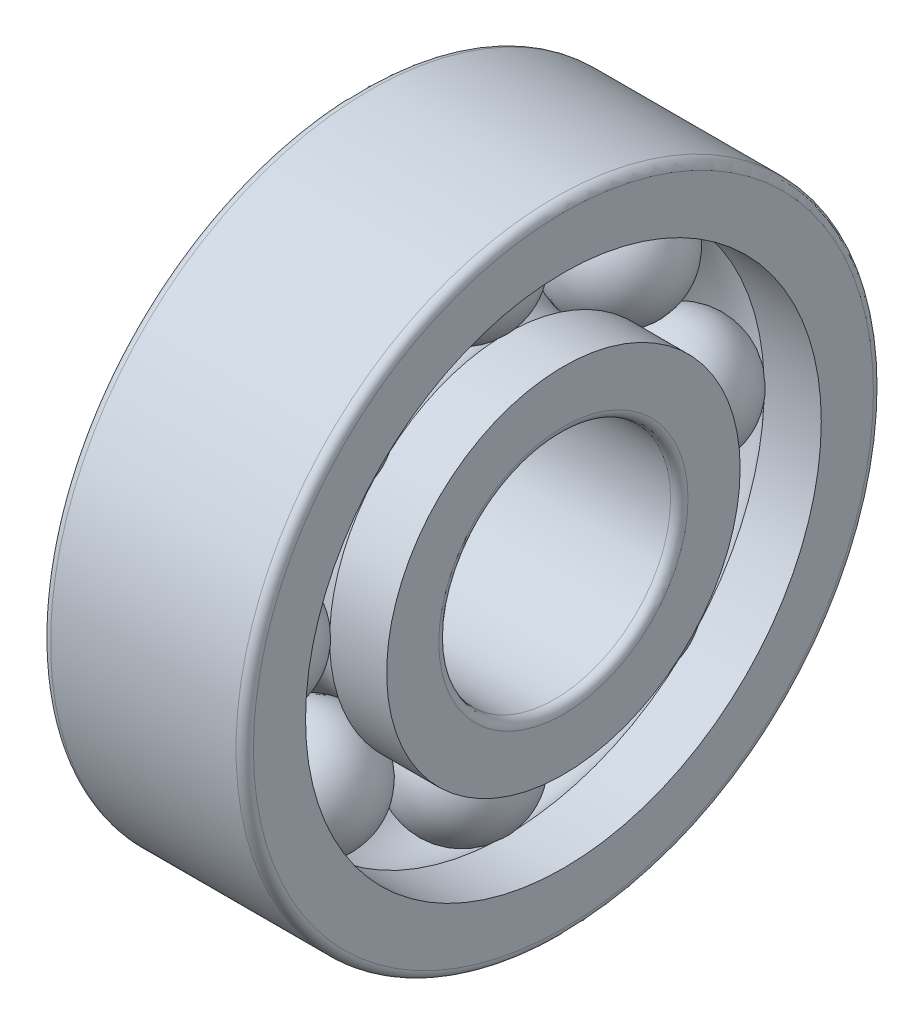
SolidWorks part; units mm, degrees
material "Alliage de zinc AC41A, brut"
ref_plane "Plane1" through (0, 0, 0) normal (0, 0, 1) x (1, 0, 0)
ref_plane "Plane2" through (0, 0, 0) normal (0, 1, 0) x (1, 0, 0)
ref_plane "Plane3" through (0, 0, 0) normal (1, 0, 0) x (0, 0, -1)
other "Configuration Table"
sketch "Clipboard" plane through (0, 0, 0) normal (0, 0, 1) x (1, 0, 0)
  line L0 (-10, 0) -> (10, 0) construction
  line L1 (0, 0) -> (22.1431, -3.112)
  line L2 (0, 0) -> (7.427, 1.0438)
  line L3 (0, 0) -> (22.1431, -3.112)
  line L4 (0, 0) -> (-22.3573, -0.3902)
  dimension "BallCLRad" = 7.5
sketch "CagSpiSke" plane through (0, 0, 0) normal (0, 0, 1) x (1, 0, 0)
  line L0 (0.21, 7.15) -> (0.21, 7.85)
  line L1 (0.21, 7.85) -> (-0.21, 7.85)
  line L2 (-0.21, 7.85) -> (-0.21, 7.15)
  line L3 (-0.21, 7.15) -> (0.21, 7.15)
  line L4 (-20.6375, 0) -> (20.6375, 0) construction
  line L5 (0, 0) -> (0, 23.7692) construction
  dimension "OD" = 15.7
  dimension "ID" = 14.3
revolve "CageSpine" add sketch "CagSpiSke" angle 0.001 about L4 reverse direction yes
ref_axis "Axis1" through (-50, 0, 0) along (1, 0, 0)
sketch "CagBalSke" plane through (0, 0, 0) normal (0, 0, 1) x (1, 0, 0)
  line L0 (-2.31, 7.5) -> (2.31, 7.5)
  line L1 (-1.905, 7.5) -> (1.905, 7.5) construction
  line L2 (-10, 0) -> (10, 0) construction
  line L3 (0, 0) -> (0, 24) construction
  arc A0 (2.31, 7.5) -> (-2.31, 7.5) centre (0, 7.5) cw
  dimension "BallCLRad" = 7.5
revolve "CageBall" [suppressed] add sketch "CagBalSke" angle 360 about L1 reverse direction yes
pattern_circular "CageBalls" [suppressed] count 8 every 45 about axis through (-50, 0, 0) along (1, 0, 0)
sketch "CagTrmODSke" plane through (0, 0, 0) normal (0, 0, 1) x (1, 0, 0)
  line L0 (2.311, 7.85) -> (2.311, 9.811)
  line L1 (2.311, 9.811) -> (-2.311, 9.811)
  line L2 (-2.311, 9.811) -> (-2.311, 7.85)
  line L3 (-2.311, 7.85) -> (2.311, 7.85)
  line L4 (-20.6375, 0) -> (20.6375, 0) construction
  line L5 (0, 0) -> (0, 25) construction
  dimension "Width" = 4.622
  dimension "ID" = 15.7
  dimension "OD" = 19.622
revolve "CageTrimOD" [suppressed] cut sketch "CagTrmODSke" angle 360 about L4 reverse direction yes
sketch "CagTrmIDSke" plane through (0, 0, 0) normal (0, 0, 1) x (1, 0, 0)
  line L0 (2.311, 5.191) -> (2.311, 7.15)
  line L1 (2.311, 7.15) -> (-2.311, 7.15)
  line L2 (-2.311, 7.15) -> (-2.311, 5.191)
  line L3 (-2.311, 5.191) -> (2.311, 5.191)
  line L4 (-20.6375, 0) -> (20.6375, 0) construction
  line L5 (0, 0) -> (0, 25) construction
  dimension "Width" = 4.622
  dimension "ID" = 10.382
  dimension "OD" = 14.3
revolve "CageTrimID" [suppressed] cut sketch "CagTrmIDSke" angle 360 about L4 reverse direction yes
sketch "BalSimSke" plane through (0, 0, 0) normal (0, 0, 1) x (1, 0, 0)
  line L0 (-10, 0) -> (10, 0) construction
  line L1 (-10, 7.5) -> (10, 7.5) construction
  line L2 (0, 0) -> (0, 23) construction
  circle A0 centre (0, 7.5) radius 2.1
  dimension "BallCLRad" = 7.5
  dimension "Ball_diameter" = 4.2
revolve "BallsSimplified" [suppressed] add sketch "BalSimSke" angle 360 about L0
sketch "BalDetSke" plane through (0, 0, 0) normal (0, 0, 1) x (1, 0, 0)
  line L0 (-2.1, 7.5) -> (2.1, 7.5)
  line L1 (-1.905, 7.5) -> (1.905, 7.5) construction
  line L2 (0, 0) -> (0, 25) construction
  arc A0 (2.1, 7.5) -> (-2.1, 7.5) centre (0, 7.5) cw
  dimension "BallCLRad" = 7.5
  dimension "Ball_diameter" = 4.2
revolve "BallDetailed" add sketch "BalDetSke" angle 360 about L1 reverse direction yes
sketch "InnRacSke" plane through (0, 0, 0) normal (0, 0, 1) x (1, 0, 0)
  line L0 (-1.5315, 6.1) -> (-3.5, 6.1)
  line L1 (-3.5, 6.1) -> (-3.5, 4.3)
  line L2 (-3.2, 4) -> (3.2, 4)
  line L3 (3.5, 4.3) -> (3.5, 6.1)
  line L4 (3.5, 6.1) -> (1.5315, 6.1)
  line L5 (-20.6375, 0) -> (20.6375, 0) construction
  line L6 (0, 0) -> (0, 30) construction
  arc A0 (-3.5, 4.3) -> (-3.2, 4) centre (-3.2, 4.3) ccw
  arc A1 (3.2, 4) -> (3.5, 4.3) centre (3.2, 4.3) ccw
  arc A2 (1.5315, 6.1) -> (-1.5315, 6.1) centre (0, 7.5) cw
  dimension "BallCLRad" = 7.5
  dimension "Fillet_radius" = 0.3
  dimension "Ball_diameter" = 4.15
  dimension "ID" = 8
  dimension "OD" = 12.2
  dimension "Width" = 7
revolve "InnerRace" add sketch "InnRacSke" angle 360 about L5 reverse direction yes
sketch "OutRacSke" plane through (0, 0, 0) normal (0, 0, 1) x (1, 0, 0)
  line L0 (-1.5315, 8.9) -> (-3.5, 8.9)
  line L1 (-3.5, 8.9) -> (-3.5, 10.7)
  line L2 (-3.2, 11) -> (3.2, 11)
  line L3 (3.5, 10.7) -> (3.5, 8.9)
  line L4 (3.5, 8.9) -> (1.5315, 8.9)
  line L5 (-20.6375, 0) -> (20.6375, 0) construction
  line L6 (0, 0) -> (0, 30) construction
  arc A0 (-3.5, 10.7) -> (-3.2, 11) centre (-3.2, 10.7) cw
  arc A1 (3.2, 11) -> (3.5, 10.7) centre (3.2, 10.7) cw
  arc A2 (1.5315, 8.9) -> (-1.5315, 8.9) centre (0, 7.5) ccw
  dimension "BallCLRad" = 7.5
  dimension "Fillet_radius" = 0.3
  dimension "Ball_diameter" = 4.15
  dimension "Width" = 7
revolve "OuterRace" add sketch "OutRacSke" angle 360 about L5 reverse direction yes
pattern_circular "BallsDetailed" count 8 every 45 about axis through (-50, 0, 0) along (1, 0, 0) of "BallDetailed"
equation "\"BallCLRad@Clipboard\" = ( \"OD@OutRacSke\" + \"ID@InnRacSke\" ) / 4"
equation "\"BallCLRad@BalSimSke\" = \"BallCLRad@Clipboard\""
equation "\"BallCLRad@BalDetSke\" = \"BallCLRad@Clipboard\""
equation "\"BallCLRad@InnRacSke\" = \"BallCLRad@Clipboard\""
equation "\"BallCLRad@OutRacSke\" = \"BallCLRad@Clipboard\""
equation "\"Ball_diameter@InnRacSke\" = \"Ball_diameter@BalDetSke\" - 0.05"
equation "\"Ball_diameter@OutRacSke\" = \"Ball_diameter@BalDetSke\" - 0.05"
equation "\"Ball_diameter@BalSimSke\" = \"Ball_diameter@BalDetSke\""
equation "\"Width@OutRacSke\" = \"Width@InnRacSke\""
equation "\"Fillet_radius@OutRacSke\" = \"Fillet_radius@InnRacSke\""
equation "\"Max_count@Clipboard\" = int( 3.14159265 / atn(( \"Ball_diameter@BalDetSke\" / 2) / sqr( \"BallCLRad@Clipboard\"  *  \"BallCLRad@Clipboard\" - ( \"Ball_diameter@BalDetSke\" / 2) *  ( \"Ball_diameter@BalDetSke\" / 2))))"
equation "\"Max_count@Clipboard\" = ((sgn( \"Max_count@Clipboard\" - \"Count@Clipboard\" )-1)*( \"Max_count@Clipboard\" - \"Count@Clipboard\" ))/-2+ \"Count@Clipboard\""
equation "\"Count@BallsDetailed\" = int( \"Show_count@Clipboard\" ) "
equation "\"Count@BallsDetailed\" = ((sgn( \"Count@BallsDetailed\" - \"Max_count@Clipboard\" )-1)*( \"Count@BallsDetailed\" - \"Max_count@Clipboard\" ))/-2+ \"Max_count@Clipboard\""
equation "\"Count@BallsDetailed\" = ((sgn( \"Count@BallsDetailed\" - \"Min_count@Clipboard\" )+1)*( \"Count@BallsDetailed\" - \"Min_count@Clipboard\"))/2 +\"Min_count@Clipboard\""
equation "\"Angle@BallsDetailed\" = 360.0 / \"Max_count@Clipboard\""
equation "\"BallCLRad@CagBalSke\" = \"BallCLRad@Clipboard\""
equation "\"Count@CageBalls\" = \"Count@BallsDetailed\""
equation "\"Angle@CageBalls\" = \"Angle@BallsDetailed\""
equation "\"Angle@CageSpine\" =  \"Angle@CageBalls\" * ( \"Count@CageBalls\" -1 + int( \"Count@CageBalls\" / \"Max_count@Clipboard\" ) )  + 0.001 -  int( \"Count@CageBalls\" / \"Max_count@Clipboard\" ) * 0.001"
equation "\"Angle@CageSpine\" =  \"Angle@CageSpine\" * int( \"Min_count@Clipboard\" / 2) + int(1 / \"Min_count@Clipboard\")  * 0.001"
equation "\"CageWallOD@CagBalSke\" =  \"Ball_diameter@BalDetSke\" * 1.1"
equation "\"Thickness@CagSpiSke\" =  \"Ball_diameter@BalDetSke\" * 0.1"
equation "\"OD@CagTrmODSke\" = \"BallCLRad@Clipboard\" * 2 + \"CageWallOD@CagBalSke\" + 0.002"
equation "\"ID@CagTrmODSke\" = \"BallCLRad@Clipboard\" * 2 + \"Ball_diameter@BalDetSke\" / 6"
equation "\"OD@CagTrmIDSke\" = \"BallCLRad@Clipboard\" * 2 - \"Ball_diameter@BalDetSke\" / 6"
equation "\"ID@CagTrmIDSke\" = \"BallCLRad@Clipboard\" * 2 - \"CageWallOD@CagBalSke\" + 0.002"
equation "\"OD@CagSpiSke\" = \"ID@CagTrmODSke\""
equation "\"ID@CagSpiSke\" = \"OD@CagTrmIDSke\""
equation "\"Width@CagTrmODSke\" = \"CageWallOD@CagBalSke\" + 0.002"
equation "\"Width@CagTrmIDSke\" = \"CageWallOD@CagBalSke\" + 0.002"
